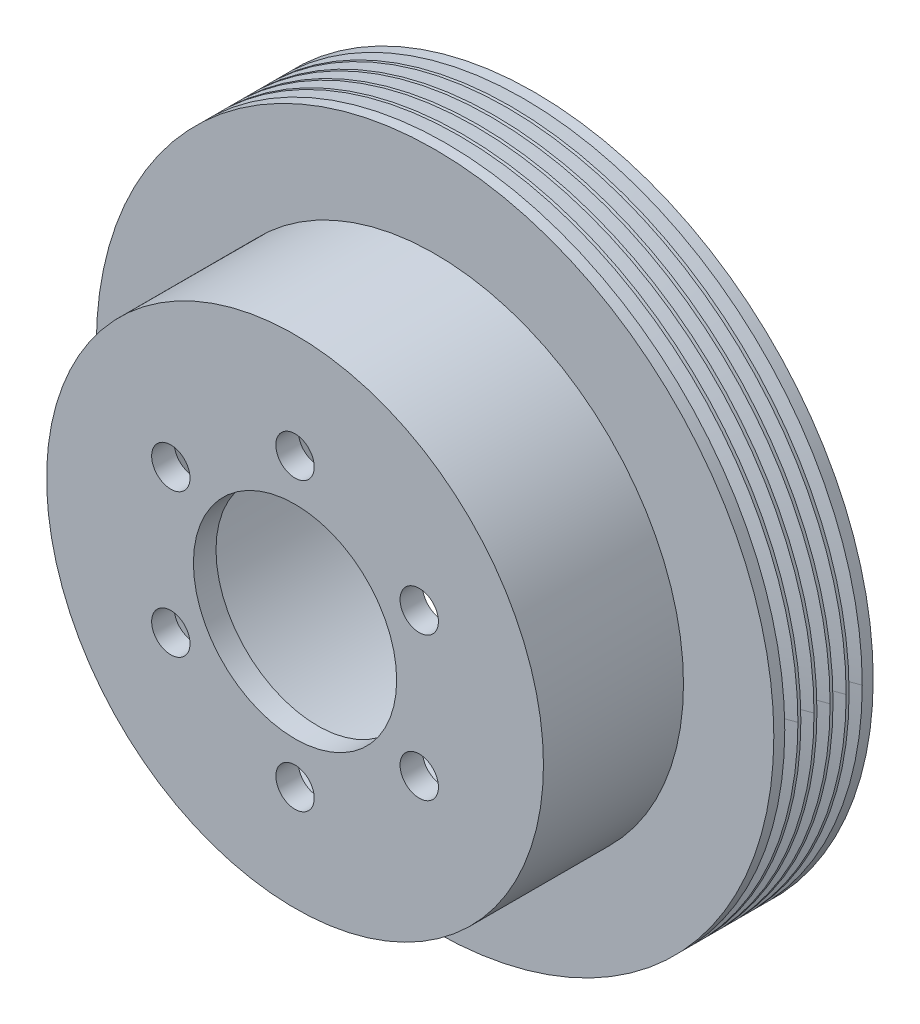
SolidWorks part; units mm, degrees
ref_plane "Plan de face" through (0, 0, 0) normal (0, 0, 1) x (1, 0, 0)
ref_plane "Plan de dessus" through (0, 0, 0) normal (0, 1, 0) x (1, 0, 0)
ref_plane "Plan de droite" through (0, 0, 0) normal (1, 0, 0) x (0, 0, -1)
sketch "Esquisse1" plane through (0, 0, 0) normal (0, 0, 1) x (1, 0, 0)
  circle A0 centre (0, 0) radius 75
  dimension "D1" = 150
extrude "Boss.-Extru.1" add sketch "Esquisse1" along normal blind 53
sketch "Esquisse2" plane through (0, 0, 53) normal (0, 0, 1) x (1, 0, 0)
  circle A0 centre (0, 0) radius 55
  circle A1 centre (0, 0) radius 75
  dimension "D1" = 110
extrude "Enlèv. mat.-Extru.1" cut sketch "Esquisse2" against normal blind 31
sketch "Esquisse3" plane through (0, 0, 0) normal (0, 0, -1) x (-1, 0, 0)
  circle A0 centre (0, 0) radius 45
  dimension "D1" = 90
extrude "Enlèv. mat.-Extru.2" cut sketch "Esquisse3" against normal blind 48
sketch "Esquisse4" plane through (0, 0, 48) normal (0, 0, -1) x (-1, 0, 0)
  circle A0 centre (0, 0) radius 22.5
  dimension "D1" = 45
extrude "Enlèv. mat.-Extru.3" cut sketch "Esquisse4" against normal blind 48
sketch "Esquisse5" plane through (0, 0, 53) normal (0, 0, 1) x (1, 0, 0)
  circle A0 centre (0, 31.75) radius 4.25
  dimension "D1" = 8.5
  dimension "D2" = 31.75
extrude "Enlèv. mat.-Extru.4" cut sketch "Esquisse5" against normal blind 48
pattern_circular "Répétition circulaire1" count 6 every 60 about axis through (0, 0, 0) along (0, 0, 1) of "Enlèv. mat.-Extru.4"
sketch "Esquisse6" plane through (0, 0, 0) normal (0, 1, 0) x (1, 0, 0)
  line L0 (-75.8905, -12.78) -> (-71, -11)
  line L1 (-71, -11) -> (-75.8905, -9.22)
  line L2 (-75.8905, -9.22) -> (-75.8905, -12.78)
  line L3 (-75, -22) -> (75, -22) construction
  dimension "D1" = 40
  dimension "D2" = 1.78
  dimension "D3" = 3.56
  dimension "D4" = 11
  dimension "D5" = 71
sweep "Enlèvement de matière-Balayage1" cut profiles "Esquisse6" path edge at (75, 0, 0)
pattern_linear "Répétition linéaire1" count 3 spacing 3.56 along (0, 0, -1) of "Enlèvement de matière-Balayage1"
pattern_linear "Répétition linéaire2" count 3 spacing 3.56 along (0, 0, 1) of "Enlèvement de matière-Balayage1"
chamfer "Chanfrein1" distance 0.8 angle 45 10 edges at (0, -71, 14.56) (0, 71, 14.56) (0, -71, 18.12) (0, 71, 18.12) (0, -71, 11) (0, 71, 11) (0, -71, 7.44) (0, 71, 7.44) (0, -71, 3.88) (0, 71, 3.88)
chamfer "Chanfrein2" distance 5 angle 45 1 edges at (-45, 0, 48)
